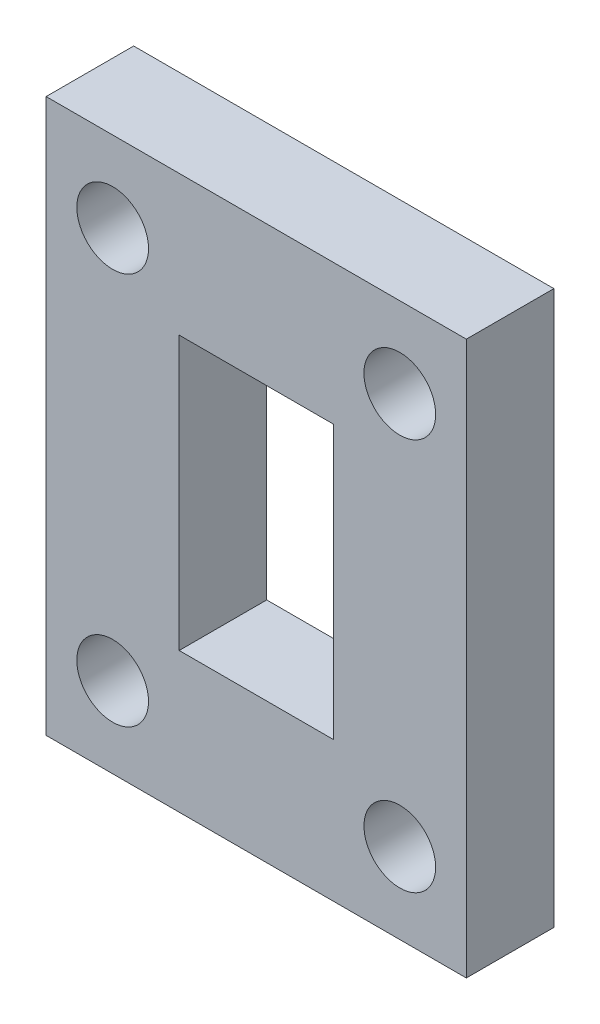
SolidWorks part; units mm, degrees
ref_plane "Front Plane" through (0, 0, 0) normal (0, 0, 1) x (1, 0, 0)
ref_plane "Top Plane" through (0, 0, 0) normal (0, 1, 0) x (1, 0, 0)
ref_plane "Right Plane" through (0, 0, 0) normal (1, 0, 0) x (0, 0, -1)
ref_axis "Axis1" through (0, 0, 0) along (0, 0, 1)
sketch "Sketch1" plane through (0, 0, 0) normal (0, 0, 1) x (1, 0, 0)
  line L1 (2.794, -4.953) -> (-2.794, -4.953) construction
  line L2 (2.794, -4.953) -> (2.794, 4.953) construction
  line L3 (2.794, 4.953) -> (-2.794, 4.953) construction
  line L4 (-2.794, -4.953) -> (-2.794, 4.953) construction
  line L5 (2.794, -4.953) -> (-2.794, 4.953) construction
  line L6 (2.794, 4.953) -> (-2.794, -4.953) construction
  line L7 (7.62, -10.033) -> (-7.62, -10.033)
  line L8 (7.62, -10.033) -> (7.62, 10.033)
  line L9 (7.62, 10.033) -> (-7.62, 10.033)
  line L10 (-7.62, -10.033) -> (-7.62, 10.033)
  line L11 (7.62, -10.033) -> (-7.62, 10.033) construction
  line L12 (7.62, 10.033) -> (-7.62, -10.033) construction
  line L13 (2.54, -4.699) -> (-2.54, -4.699) construction
  line L14 (2.54, -4.699) -> (2.54, 4.699) construction
  line L15 (2.54, 4.699) -> (-2.54, 4.699) construction
  line L16 (-2.54, -4.699) -> (-2.54, 4.699) construction
  line L17 (2.54, -4.699) -> (-2.54, 4.699) construction
  line L18 (2.54, 4.699) -> (-2.54, -4.699) construction
  line L19 (-2.794, 4.953) -> (2.794, 4.953)
  line L20 (-2.794, 4.953) -> (-2.794, -4.953)
  line L21 (-2.794, -4.953) -> (2.794, -4.953)
  line L22 (2.794, 4.953) -> (2.794, -4.953)
  point P0 (0, 0)
  point P6 (0, 0)
  point P11 (0, 0)
  dimension "D1" = 5.588
  dimension "D2" = 9.906
  dimension "D3" = 5.08
  dimension "D4" = 9.398
  dimension "D5" = 5.08
  dimension "D6" = 5.08
extrude "Boss-Extrude1" add sketch "Sketch1" along normal blind 3.175
sketch "Sketch2" plane through (0, 0, 3.175) normal (0, 0, 1) x (1, 0, 0)
  line L0 (0, 10.033) -> (0, -10.033) construction
  line L1 (7.62, 10.033) -> (-7.62, 10.033) construction
  line L2 (-7.62, -10.033) -> (7.62, -10.033) construction
  line L3 (-7.62, 0) -> (7.62, 0) construction
  line L4 (-7.62, 10.033) -> (-7.62, -10.033) construction
  line L5 (7.62, -10.033) -> (7.62, 10.033) construction
  line L6 (-7.62, 0) -> (-2.794, 0) construction
  line L7 (-2.794, 4.953) -> (-2.794, -4.953) construction
  circle A0 centre (-5.207, 7.112) radius 1.3
  circle A1 centre (5.207, 7.112) radius 1.3
  circle A2 centre (5.207, -7.112) radius 1.3
  circle A3 centre (-5.207, -7.112) radius 1.3
  point P25 (-5.207, 0)
  dimension "D1" = 2.6
  dimension "D2" = 5.207
  dimension "D3" = 7.112
extrude "Cut-Extrude1" cut sketch "Sketch2" against normal up to next
equation "\"t\"=0.125"
equation "\"D1@Boss-Extrude1\"=\"t\""
